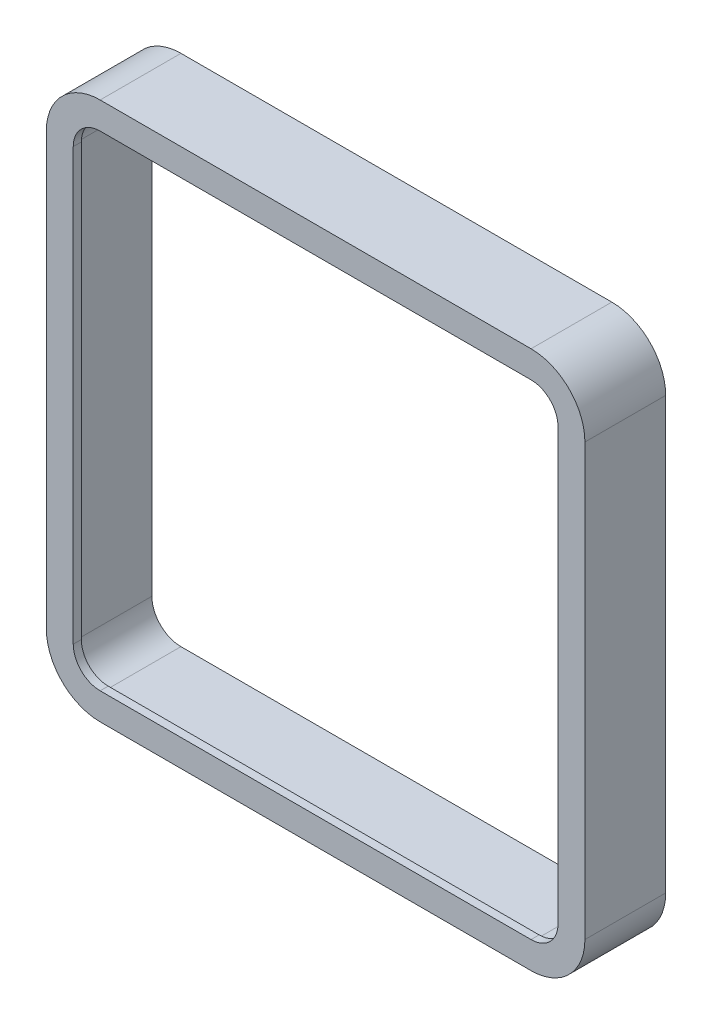
SolidWorks part; units mm, degrees
ref_plane "Piano frontale" through (0, 0, 0) normal (0, 0, 1) x (1, 0, 0)
ref_plane "Piano superiore" through (0, 0, 0) normal (0, 1, 0) x (1, 0, 0)
ref_plane "Piano destro" through (0, 0, 0) normal (1, 0, 0) x (0, 0, -1)
sketch "Sketch2" plane through (0, 0, 0) normal (0, 0, 1) x (1, 0, 0)
  line L5 (-100, -100) -> (100, -100)
  line L6 (-100, -100) -> (-100, 100)
  line L7 (-100, 100) -> (100, 100)
  line L8 (100, -100) -> (100, 100)
  line L9 (-100, -100) -> (100, 100) construction
  line L10 (-100, 100) -> (100, -100) construction
  point P0 (0, 0)
  dimension "D1" = 200
extrude "Boss-Extrude1" add sketch "Sketch2" along normal blind 30
fillet "Fillet1" radius 20 4 edges at (-100, -100, 15) (100, -100, 15) (100, 100, 15) (-100, 100, 15)
sketch "Sketch3" plane through (0, 0, 30) normal (0, 0, 1) x (1, 0, 0)
  line L8 (-90, 80) -> (-90, -80)
  line L9 (-80, -90) -> (80, -90)
  line L10 (90, -80) -> (90, 80)
  line L11 (80, 90) -> (-80, 90)
  line L12 (-90, 80) -> (-90, -80)
  line L13 (-80, -90) -> (80, -90)
  line L14 (90, -80) -> (90, 80)
  line L15 (80, 90) -> (-80, 90)
  arc A8 (-90, -80) -> (-80, -90) centre (-80, -80) ccw
  arc A9 (80, -90) -> (90, -80) centre (80, -80) ccw
  arc A10 (90, 80) -> (80, 90) centre (80, 80) ccw
  arc A11 (-80, 90) -> (-90, 80) centre (-80, 80) ccw
  arc A12 (-90, -80) -> (-80, -90) centre (-80, -80) ccw
  arc A13 (80, -90) -> (90, -80) centre (80, -80) ccw
  arc A14 (90, 80) -> (80, 90) centre (80, 80) ccw
  arc A15 (-80, 90) -> (-90, 80) centre (-80, 80) ccw
  dimension "D1" = 10
extrude "Cut-Extrude1" cut sketch "Sketch3" against normal blind 3
sketch "Sketch4" plane through (0, 0, 27) normal (0, 0, 1) x (1, 0, 0)
  line L8 (-90.8, 80) -> (-90.8, -80)
  line L9 (-80, -90.8) -> (80, -90.8)
  line L10 (90.8, -80) -> (90.8, 80)
  line L11 (80, 90.8) -> (-80, 90.8)
  line L12 (-90.8, 80) -> (-90.8, -80)
  line L13 (-80, -90.8) -> (80, -90.8)
  line L14 (90.8, -80) -> (90.8, 80)
  line L15 (80, 90.8) -> (-80, 90.8)
  arc A8 (-80, 90.8) -> (-90.8, 80) centre (-80, 80) ccw
  arc A9 (-90.8, -80) -> (-80, -90.8) centre (-80, -80) ccw
  arc A10 (80, -90.8) -> (90.8, -80) centre (80, -80) ccw
  arc A11 (90.8, 80) -> (80, 90.8) centre (80, 80) ccw
  arc A12 (-80, 90.8) -> (-90.8, 80) centre (-80, 80) ccw
  arc A13 (-90.8, -80) -> (-80, -90.8) centre (-80, -80) ccw
  arc A14 (80, -90.8) -> (90.8, -80) centre (80, -80) ccw
  arc A15 (90.8, 80) -> (80, 90.8) centre (80, 80) ccw
  dimension "D1" = 0.8
extrude "Cut-Extrude2" cut sketch "Sketch4" against normal through all
